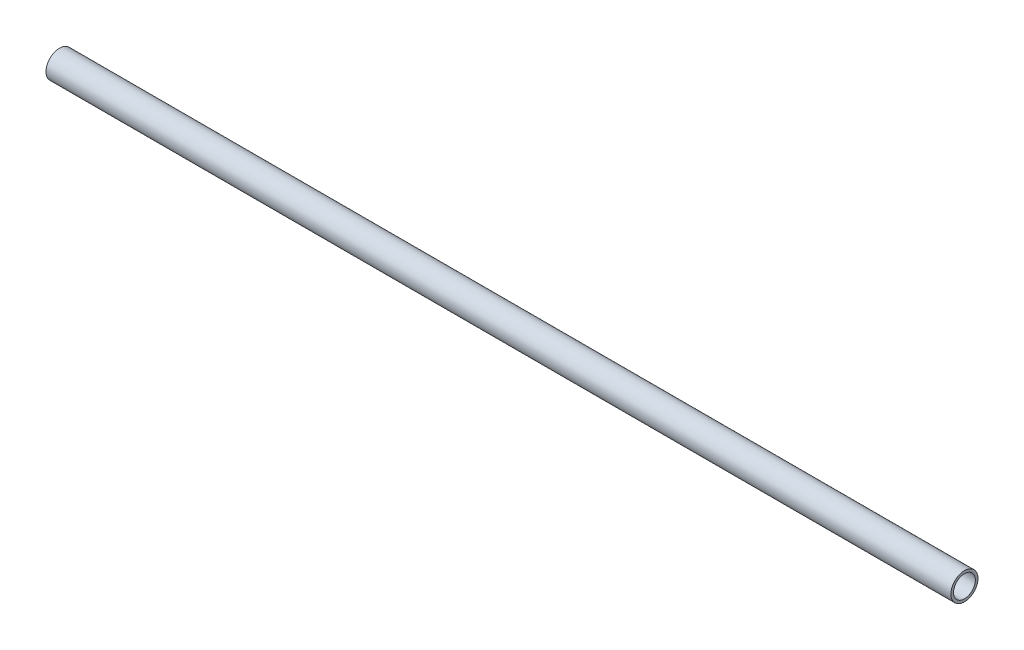
SolidWorks part; units mm, degrees
ref_plane "Front Plane" through (0, 0, 0) normal (0, 0, 1) x (1, 0, 0)
ref_plane "Top Plane" through (0, 0, 0) normal (0, 1, 0) x (1, 0, 0)
ref_plane "Right Plane" through (0, 0, 0) normal (1, 0, 0) x (0, 0, -1)
sketch "Sketch1" plane through (0, 0, 0) normal (1, 0, 0) x (0, 0, -1)
  circle A0 centre (0, 0) radius 6.35
  circle A1 centre (0, 0) radius 5.1054
  dimension "D1" = 12.7
  dimension "D2" = 10.2108
extrude "Boss-Extrude1" add sketch "Sketch1" along normal blind 424.1241
